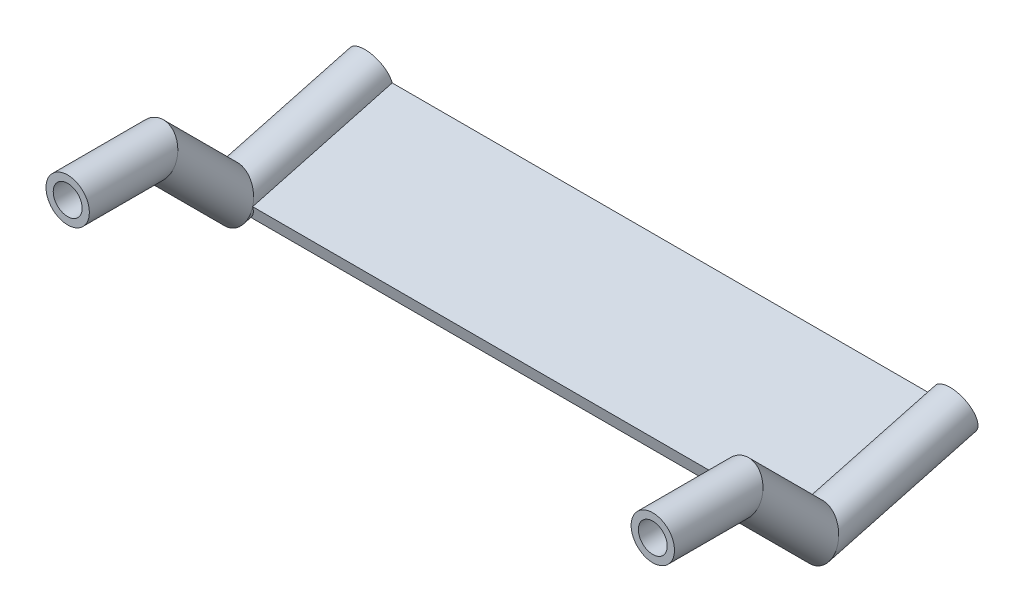
SolidWorks part; units mm, degrees
ref_plane "Front Plane" through (0, 0, 0) normal (0, 0, 1) x (1, 0, 0)
ref_plane "Top Plane" through (0, 0, 0) normal (0, 1, 0) x (1, 0, 0)
ref_plane "Right Plane" through (0, 0, 0) normal (1, 0, 0) x (0, 0, -1)
sketch "Sketch2" plane through (0, 0, 0) normal (1, 0, 0) x (0, 0, -1)
  line L0 (0, 0) -> (120, 0)
  line L1 (120, 0) -> (226.066, -106.066)
  line L2 (226.066, -106.066) -> (419.2512, -54.3022)
  dimension "D1" = 120
  dimension "D2" = 45
  dimension "D3" = 120
  dimension "D4" = 150
  dimension "D5" = 200
sweep "Sweep-Thin1" add path "Sketch2" circular profile diameter 60 parameters "D1"=10, "D3"=60
sketch "Sketch13" plane through (0, 0, 0) normal (1, 0, 0) x (0, 0, -1)
  line L0 (226.066, -106.066) -> (419.2512, -54.3022)
  line L1 (217.1003, -139.5267) -> (235.0318, -72.6054) construction
  line L2 (424.4276, -73.6207) -> (414.0748, -34.9837) construction
extrude "Extrude-Thin1" add sketch "Sketch13" along normal blind 760 from offset 20 thin thin type one direction wall 20
ref_plane "Plane1" through (405, 0, 0) normal (1, 0, 0) x (0, 0, -1)
mirror "Mirror4" about plane through (405, 0, 0) normal (1, 0, 0) of bodies 102
